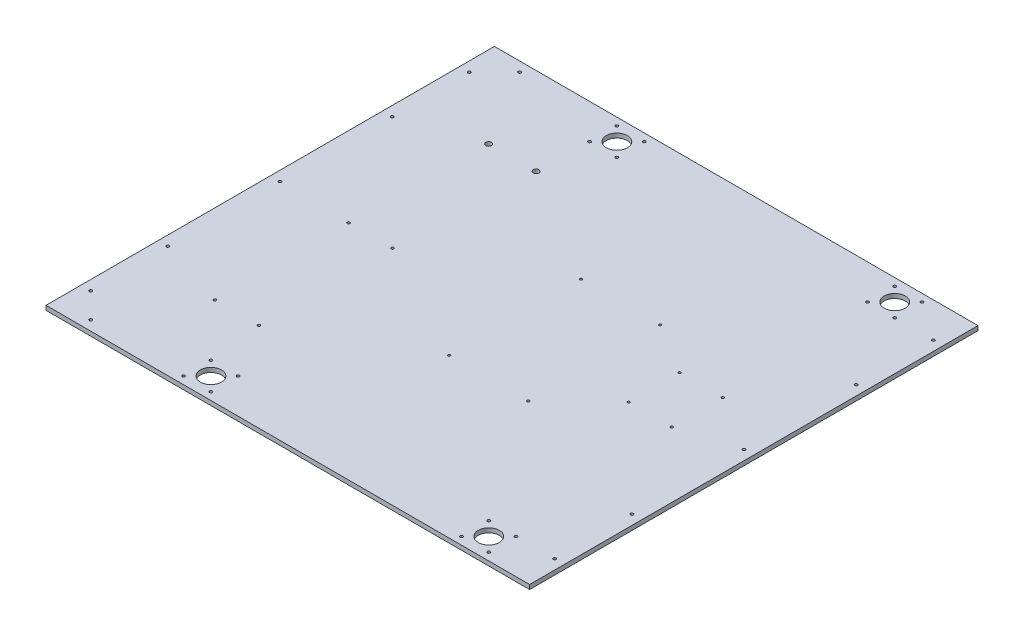
SolidWorks part; units mm, degrees
ref_plane "Front Plane" through (0, 0, 0) normal (0, 0, 1) x (1, 0, 0)
ref_plane "Top Plane" through (0, 0, 0) normal (0, 1, 0) x (1, 0, 0)
ref_plane "Right Plane" through (0, 0, 0) normal (1, 0, 0) x (0, 0, -1)
sketch "Sketch1" plane through (0, 0, 0) normal (1, 0, 0) x (0, 0, -1)
  line L0 (0, 0) -> (-510, 0)
  line L1 (-510, 0) -> (-510, 5)
  line L2 (-510, 5) -> (0, 5)
  line L6 (0, 5) -> (0, 0)
  dimension "D1" = 510
  dimension "D2" = 5
extrude "Boss-Extrude1" add sketch "Sketch1" along normal blind 550
sketch "BotthomHoles-Sketch2" plane through (0, 5, 0) normal (0, 1, 0) x (1, 0, 0)
  line L0 (550, -3.175) -> (0, -3.175) construction
  line L2 (550, 0) -> (550, -510) construction
  line L3 (550, 0) -> (0, 0) construction
  line L4 (550, -510) -> (0, -510) construction
  line L7 (0, 0) -> (0, -510) construction
  line L8 (550, 0) -> (550, -510) construction
  circle A0 centre (479.425, -24.175) radius 12
  circle A2 centre (463.925, -8.675) radius 1.5875
  circle A3 centre (494.925, -8.675) radius 1.5875
  circle A6 centre (463.925, -39.675) radius 1.5875
  circle A7 centre (494.925, -39.675) radius 1.5875
  circle A8 centre (39.6875, -11.1125) radius 1.5875
  circle A10 centre (178.925, -39.675) radius 1.5875
  circle A11 centre (147.925, -39.675) radius 1.5875
  circle A12 centre (178.925, -8.675) radius 1.5875
  circle A13 centre (147.925, -8.675) radius 1.5875
  circle A14 centre (163.425, -24.175) radius 12
  circle A15 centre (39.6875, -498.8875) radius 1.5875
  circle A16 centre (147.925, -501.325) radius 1.5875
  circle A17 centre (178.925, -501.325) radius 1.5875
  circle A18 centre (147.925, -470.325) radius 1.5875
  circle A19 centre (178.925, -470.325) radius 1.5875
  circle A20 centre (463.925, -470.325) radius 1.5875
  circle A21 centre (463.925, -501.325) radius 1.5875
  circle A22 centre (494.925, -470.325) radius 1.5875
  circle A23 centre (494.925, -501.325) radius 1.5875
  circle A25 centre (163.425, -485.825) radius 12
  circle A26 centre (479.425, -485.825) radius 12
  circle A27 centre (11.1125, -39.6875) radius 1.5875
  circle A28 centre (11.1125, -127.5) radius 1.5875
  circle A29 centre (11.1125, -255) radius 1.5875
  circle A30 centre (11.1125, -382.5) radius 1.5875
  circle A31 centre (11.1125, -470.3125) radius 1.5875
  circle A32 centre (538.8875, -470.3125) radius 1.5875
  circle A33 centre (538.8875, -382.5) radius 1.5875
  circle A34 centre (538.8875, -255) radius 1.5875
  circle A35 centre (538.8875, -127.5) radius 1.5875
  circle A36 centre (538.8875, -39.6875) radius 1.5875
  dimension "D9" = 3.175
  dimension "D10" = 24
  dimension "D13" = 3.175
  dimension "D29" = 3.175
  dimension "D2" = 8.675
  dimension "D5" = 15.5
  dimension "D6" = 31
  dimension "D7" = 15.5
  dimension "D8" = 31
  dimension "D11" = 21
  dimension "D12" = 39.6875
  dimension "D15" = 31
  dimension "D16" = 15.5
  dimension "D17" = 316
  dimension "D3" = 70.575
  dimension "D4" = 11.1125
  dimension "D18" = 8.675
  dimension "D19" = 15.5
  dimension "D20" = 31
  dimension "D21" = 11.1125
  dimension "D22" = 39.6875
  dimension "D23" = 39.6875
  dimension "D24" = 127.5
  dimension "D25" = 127.5
  dimension "D26" = 127.5
  dimension "D27" = 11.1125
  dimension "D28" = 11.1125
extrude "BottomHoles-Cut-Extrude1" cut sketch "BotthomHoles-Sketch2" against normal through all
sketch "BottomPSUHolesSketch2" plane through (0, 5, 0) normal (0, 1, 0) x (1, 0, 0)
  line L0 (0, 0) -> (0, -510) construction
  line L3 (550, 0) -> (0, 0) construction
  line L4 (550, -510) -> (0, -510) construction
  circle A0 centre (90.8, -256.7) radius 1.5
  circle A1 centre (140.8, -256.7) radius 1.5
  circle A2 centre (90.8, -408.7) radius 1.5
  circle A3 centre (140.8, -408.7) radius 1.5
  circle A6 centre (92.8, -99.3) radius 3.25
  circle A7 centre (146.8, -99.3) radius 3.25
  dimension "D6" = 3
  dimension "D4" = 6.5
  dimension "D1" = 152
  dimension "D2" = 50
  dimension "D3" = 90.8
  dimension "D7" = 54
  dimension "D8" = 2
  dimension "D9" = 99.3
  dimension "D5" = 101.3
extrude "BottomPSUHolesCut-Extrude1" cut sketch "BottomPSUHolesSketch2" against normal through all
sketch "BottomMainboardHolesSketch2" plane through (0, 5, 0) normal (0, 1, 0) x (1, 0, 0)
  line L0 (550, 0) -> (0, 0) construction
  line L1 (0, 0) -> (0, -510) construction
  line L2 (550, 0) -> (550, -510) construction
  line L3 (550, -510) -> (0, -510) construction
  circle A0 centre (278.5, -180) radius 1.35
  circle A1 centre (368.5, -180) radius 1.35
  circle A2 centre (278.5, -330) radius 1.35
  circle A3 centre (368.5, -330) radius 1.35
  circle A4 centre (426.7, -216) radius 1.35
  circle A5 centre (475.7, -216) radius 1.35
  circle A6 centre (426.7, -274) radius 1.35
  circle A7 centre (475.7, -274) radius 1.35
  dimension "D6" = 2.7
  dimension "D7" = 2.7
  dimension "D1" = 90
  dimension "D2" = 150
  dimension "D3" = 180
  dimension "D4" = 58
  dimension "D5" = 49
  dimension "D8" = 216
  dimension "D9" = 278.5
  dimension "D10" = 74.3
  dimension "D11" = 236
extrude "BottomMainboardHolesCut-Extrude1" cut sketch "BottomMainboardHolesSketch2" against normal through all
equation "\"LowerRailWidth\"= 2.00in"
equation "\"RailThickness\"= .125in'Spec"
equation "\"StepperHoleDiameter\"= 24mm"
equation "\"StepperMountingHoleDiameter\"= 3.175mm"
equation "\"SideRailLength\"= 550mm"
equation "\"StepperMountingHoleDistance\"= 31mm'Spec"
equation "\"StepperMountingHoleOffsetFromLeftOrRightSide\"= \"StepperMountingHoleOffsetFromItsSide\" + \"RailThickness\""
equation "\"HoleOffsetFromEdge\"= \"RailThickness\" * 2.5"
equation "\"HoleOffsetFromSide\"= \"RailThickness\" * 3.5"
equation "\"StepperMountingHoleOffsetFromItsSide\"= 5.5mm'Spec"
equation "\"FasteningHoleDiameter\"= .125in"
equation "\"D2@BotthomHoles-Sketch2\" = \"StepperMountingHoleOffsetFromLeftOrRightSide\""
equation "\"D5@BotthomHoles-Sketch2\" = \"StepperMountingHoleDistance\" / 2"
equation "\"D6@BotthomHoles-Sketch2\" = \"StepperMountingHoleDistance\""
equation "\"D7@BotthomHoles-Sketch2\" = \"StepperMountingHoleDistance\" / 2"
equation "\"D8@BotthomHoles-Sketch2\" = \"StepperMountingHoleDistance\""
equation "\"D9@BotthomHoles-Sketch2\" = \"StepperMountingHoleDiameter\""
equation "\"D10@BotthomHoles-Sketch2\" = \"StepperHoleDiameter\""
equation "\"D1@Boss-Extrude1\"=\"SideRailLength\""
equation "\"BedThirdSize\"= 70mm"
equation "\"BedInnerSquareWidth\"= \"BedThirdSize\" * 3'Equals 210"
equation "\"BedInnerSquareLength\"= \"BedInnerSquareWidth\""
equation "\"BedLWidth\"= \"BedThirdSize\"'Equals 70"
equation "\"BedLength\"= \"BedInnerSquareLength\" + \"BedLWidth\" * 2 + \"BedIncreasedByLength\"'Equals 350"
equation "\"DistanceBetweenFrontToBackStepperHoles\"= \"BedLength\" - \"DistanceFromBedFrontToFirstLeftStepperHole\"'Equals 316"
equation "\"DistanceFromBedFrontToFirstLeftStepperHole\"= \"LeadScrewNutPadSize\" + 10mm'Equals 34"
equation "\"DistanceFromFrontSideToBedFront\"= \"RailThickness\" + \"BeltTensionerDepth\" + 10mm'Equals 36.575"
equation "\"20TGT2PulleyDiameter\"= 17.9mm'Spec"
equation "\"BeltTensionerBackWallThickness\"= 4mm"
equation "\"BeltTensionerSpaceBetweenPulleyAndWall\"= 1.5mm"
equation "\"BeltTensionerInnerDepth\"= \"20TGT2PulleyDiameter\" + \"BeltTensionerSpaceBetweenPulleyAndWall\""
equation "\"BeltTensionerDepth\"= \"BeltTensionerBackWallThickness\" + \"BeltTensionerInnerDepth\"'Equals 23.4"
equation "\"BedIncreasedByLength\"= 0mm"
equation "\"LowerCornerBlockWidth\"= \"LowerRailWidth\" - \"RailThickness\" * 2'Room for left front stepper"
equation "\"D12@BotthomHoles-Sketch2\"=\"CornerEnclosureOffset\""
equation "\"D13@BotthomHoles-Sketch2\"=\"FasteningHoleDiameter\""
equation "\"CornerEnclosureOffset\"= \"LowerCornerBlockWidth\" - \"HoleOffsetFromEdge\" + \"RailThickness\""
equation "\"LowerCornerBlockY1FromSide\"= \"HoleOffsetFromSide\""
equation "\"D15@BotthomHoles-Sketch2\"=\"StepperMountingHoleDistance\""
equation "\"D16@BotthomHoles-Sketch2\"=\"StepperMountingHoleDistance\"/2"
equation "\"D17@BotthomHoles-Sketch2\"=\"DistanceBetweenFrontToBackStepperHoles\""
equation "\"DistanceFromFrontSideToFirstLeftStepperHole\"= \"DistanceFromFrontSideToBedFront\" + \"DistanceFromBedFrontToFirstLeftStepperHole\"'Equals 70.575"
equation "\"LeadScrewNutMountingHoleFlangeDiameter\"= 22mm'Spec"
equation "\"LeadScrewNutPadSize\"= \"LeadScrewNutMountingHoleFlangeDiameter\" + 2mm'Equals 24"
equation "\"D3@BotthomHoles-Sketch2\"=\"DistanceFromFrontSideToFirstLeftStepperHole\""
equation "\"LowerEnclosureThickness\"= 5mm"
equation "\"FrontBackRailLength\"= 510mm"
equation "\"D4@BotthomHoles-Sketch2\"=\"LowerCornerBlockY1FromSide\""
equation "\"D1@Sketch1\"=\"FrontBackRailLength\""
equation "\"D18@BotthomHoles-Sketch2\"=\"StepperMountingHoleOffsetFromLeftOrRightSide\""
equation "\"D19@BotthomHoles-Sketch2\"=\"StepperMountingHoleDistance\"/2"
equation "\"D20@BotthomHoles-Sketch2\"=\"StepperMountingHoleDistance\""
equation "\"D21@BotthomHoles-Sketch2\"=\"LowerCornerBlockY1FromSide\""
equation "\"D22@BotthomHoles-Sketch2\"=\"CornerEnclosureOffset\""
equation "\"D23@BotthomHoles-Sketch2\"=\"CornerEnclosureOffset\""
equation "\"FrontOrBackEnclosureOffsets\"= \"FrontBackRailLength\" / 4"
equation "\"D24@BotthomHoles-Sketch2\"=\"FrontOrBackEnclosureOffsets\""
equation "\"D25@BotthomHoles-Sketch2\"=\"FrontOrBackEnclosureOffsets\""
equation "\"D26@BotthomHoles-Sketch2\"=\"FrontOrBackEnclosureOffsets\""
equation "\"D27@BotthomHoles-Sketch2\"=\"LowerCornerBlockY1FromSide\""
equation "\"D28@BotthomHoles-Sketch2\"=\"LowerCornerBlockY1FromSide\""
equation "\"D29@BotthomHoles-Sketch2\"=\"FasteningHoleDiameter\""
equation "\"D2@Sketch1\"=\"LowerEnclosureThickness\""
equation "\"24VPSUMountingHolesShortDistanceBetween\"= 50mm'Yours may differ"
equation "\"24VPSUMountingHolesLongDistanceBetween\"= 152mm'Yours may differ"
equation "\"24VPSUMountingHoleOffsetFromEitherSide\"= 30mm'Yours may differ"
equation "\"24VPSUMountingHoleOffsetFromEdge\"= \"24VPSUMountingHoleOffsetFromEitherSide\" + \"LowerRailWidth\" + 10mm'Yours may differ"
equation "\"24VPSUMountingHoleDiameter\"= 3mm'Yours may differ"
equation "\"D2@BottomPSUHolesSketch2\" = \"24VPSUMountingHolesShortDistanceBetween\""
equation "\"D1@BottomPSUHolesSketch2\" = \"24VPSUMountingHolesLongDistanceBetween\""
equation "\"D3@BottomPSUHolesSketch2\" = \"24VPSUMountingHoleOffsetFromEdge\""
equation "\"D6@BottomPSUHolesSketch2\" = \"24VPSUMountingHoleDiameter\""
equation "\"RPi4BoardLength\"= 85mm'Spec"
equation "\"RPi4BoardWidth\"= 56mm'Spec"
equation "\"RPi4BoardMountingHoleOffsetFromEdge\"= 3.5mm'Spec"
equation "\"RPi4BoardMountingHoleDiameter\"= 2.7mm'Spec"
equation "\"OctopusV1.1BoardMountingHoleOffsetFromAllEdges\"= 3.5mm'Spec"
equation "\"OctopusV1.1BoardMountingHoleLengthDistanceBetween\"= 150mm'Spec"
equation "\"OctopusV1.1BoardMountingHoleWidthDistanceBetween\"= 90mm'Spec"
equation "\"D2@BottomMainboardHolesSketch2\" = \"OctopusV1.1BoardMountingHoleLengthDistanceBetween\""
equation "\"D3@BottomMainboardHolesSketch2\" =  ( \"FrontBackRailLength\" - \"OctopusV1.1BoardMountingHoleLengthDistanceBetween\" )  / 2"
equation "\"D4@BottomMainboardHolesSketch2\" = \"RPi4BoardMountingHoleLengthDistanceBetween\""
equation "\"D5@BottomMainboardHolesSketch2\"=\"RPi4BoardWidth\"- \"RPi4BoardMountingHoleOffsetFromEdge\" * 2"
equation "\"D6@BottomMainboardHolesSketch2\" = \"OctopusV1.1BoardMountingHoleDiameter\""
equation "\"D7@BottomMainboardHolesSketch2\" = \"RPi4BoardMountingHoleDiameter\""
equation "\"RPi4BoardMountingHoleLengthDistanceBetween\"= 58mm'Spec"
equation "\"OctopusV1.1BoardMountingHoleDiameter\"= 2.7mm'Spec"
equation "\"D1@BottomMainboardHolesSketch2\" = \"OctopusV1.1BoardMountingHoleWidthDistanceBetween\""
equation "\"D8@BottomMainboardHolesSketch2\" =  ( \"FrontBackRailLength\" - \"RPi4BoardLength\" )  / 2 + \"RPi4BoardMountingHoleOffsetFromEdge\""
equation "\"D9@BottomMainboardHolesSketch2\" = \"SideRailLength\" / 2 + \"OctopusV1.1BoardMountingHoleOffsetFromAllEdges\""
equation "\"D10@BottomMainboardHolesSketch2\"= \"LowerRailWidth\" + \"RPi4BoardMountingHoleOffsetFromEdge\" + \"EnclosurePartsOffsetFromFrameInnerEdge\""
equation "\"RCNUN5VMountingHoleDiameter\"= 6.5mm'Spec"
equation "\"RCNUN5VHeight\"= 57mm'Spec"
equation "\"RCNUN5VMountingHoleWidthDistance\"= 54mm'Spec. STL Is incorrect?"
equation "\"D4@BottomPSUHolesSketch2\"=\"RCNUN5VMountingHoleDiameter\""
equation "\"D7@BottomPSUHolesSketch2\"=\"RCNUN5VMountingHoleWidthDistance\""
equation "\"D8@BottomPSUHolesSketch2\"=(\"RCNUN5VMountingHoleWidthDistance\" - \"24VPSUMountingHolesShortDistanceBetween\")/2"
equation "\"D9@BottomPSUHolesSketch2\"=\"LowerRailWidth\" + \"RCNUN5VHeight\"/2 + \"EnclosurePartsOffsetFromFrameInnerEdge\""
equation "\"EnclosurePartsOffsetFromFrameInnerEdge\"= 20mm"
equation "\"D5@BottomPSUHolesSketch2\"= \"LowerRailWidth\" + \"EnclosurePartsOffsetFromFrameInnerEdge\" + ( \"24VPSULength\" - \"24VPSUMountingHolesLongDistanceBetween\" ) / 2"
equation "\"24VPSULength\"= 213mm'Spec"
